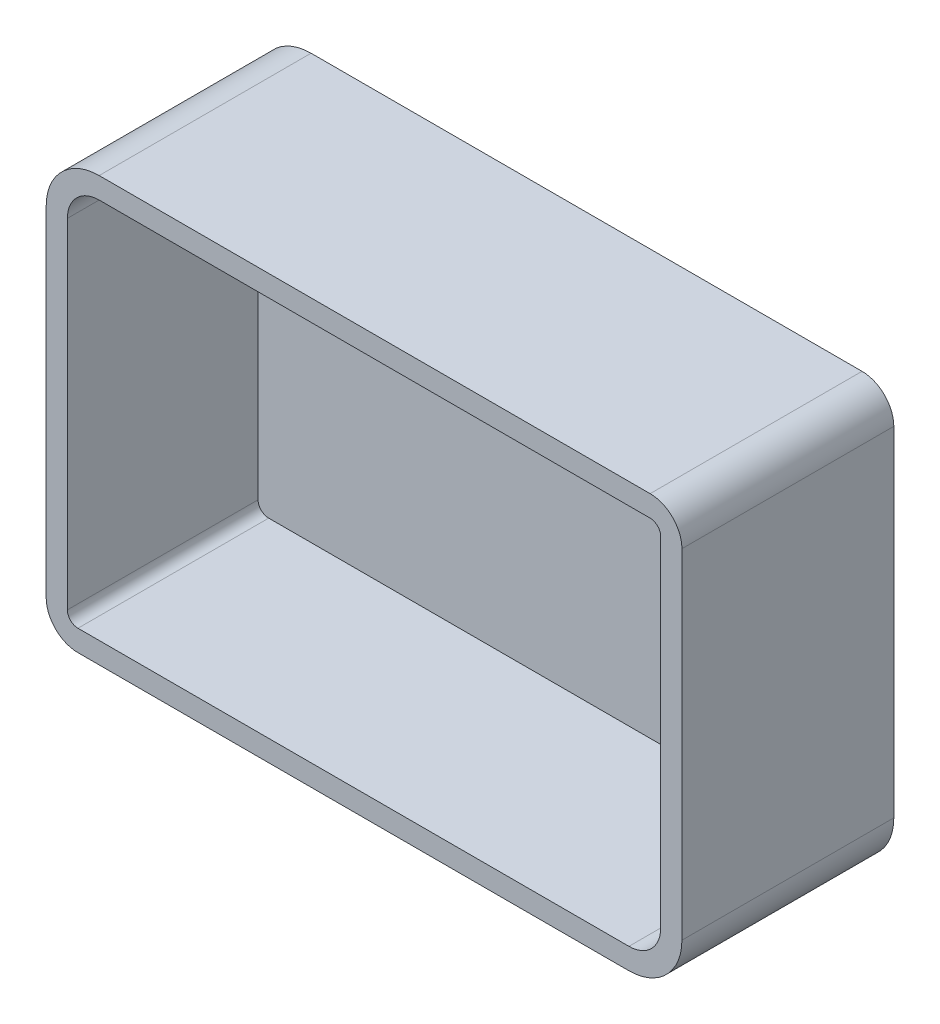
SolidWorks part; units mm, degrees
ref_plane "Front Plane" through (0, 0, 0) normal (0, 0, 1) x (1, 0, 0)
ref_plane "Top Plane" through (0, 0, 0) normal (0, 1, 0) x (1, 0, 0)
ref_plane "Right Plane" through (0, 0, 0) normal (1, 0, 0) x (0, 0, -1)
sketch "Sketch1" plane through (0, 0, 0) normal (0, 0, 1) x (1, 0, 0)
  line L1 (-190.5, -127) -> (190.5, -127)
  line L2 (-190.5, -127) -> (-190.5, 127)
  line L3 (-190.5, 127) -> (190.5, 127)
  line L4 (190.5, -127) -> (190.5, 127)
  line L5 (-190.5, -127) -> (190.5, 127) construction
  line L6 (-190.5, 127) -> (190.5, -127) construction
  point P0 (0, 0)
  dimension "D1" = 381
  dimension "D2" = 254
extrude "Boss-Extrude1" add sketch "Sketch1" against normal blind 127
fillet "Fillet5" radius 19.05 2 edges at (-190.5, -127, -63.5) (190.5, 127, -63.5)
fillet "Fillet4" radius 31.75 2 edges at (190.5, -127, -63.5) (-190.5, 127, -63.5)
sketch "Sketch3" plane through (0, 0, 0) normal (0, 0, -1) x (-1, 0, 0)
  line L16 (-158.75, -114.3) -> (171.45, -114.3)
  line L17 (-177.8, 107.95) -> (-177.8, -95.25)
  line L18 (158.75, 114.3) -> (-171.45, 114.3)
  line L19 (177.8, -107.95) -> (177.8, 95.25)
  line L20 (-158.75, -114.3) -> (171.45, -114.3)
  line L21 (-177.8, 107.95) -> (-177.8, -95.25)
  line L22 (158.75, 114.3) -> (-171.45, 114.3)
  line L23 (177.8, -107.95) -> (177.8, 95.25)
  arc A13 (-177.8, -95.25) -> (-158.75, -114.3) centre (-158.75, -95.25) ccw
  arc A14 (-171.45, 114.3) -> (-177.8, 107.95) centre (-171.45, 107.95) ccw
  arc A15 (177.8, 95.25) -> (158.75, 114.3) centre (158.75, 95.25) ccw
  arc A16 (171.45, -114.3) -> (177.8, -107.95) centre (171.45, -107.95) ccw
  arc A17 (-177.8, -95.25) -> (-158.75, -114.3) centre (-158.75, -95.25) ccw
  arc A18 (-171.45, 114.3) -> (-177.8, 107.95) centre (-171.45, 107.95) ccw
  arc A19 (177.8, 95.25) -> (158.75, 114.3) centre (158.75, 95.25) ccw
  arc A20 (171.45, -114.3) -> (177.8, -107.95) centre (171.45, -107.95) ccw
  dimension "D1" = 12.7
extrude "Cut-Extrude1" cut sketch "Sketch3" along normal offset from surface (114.3 mm away) 12.7 up to face at (0, 0, -127)
